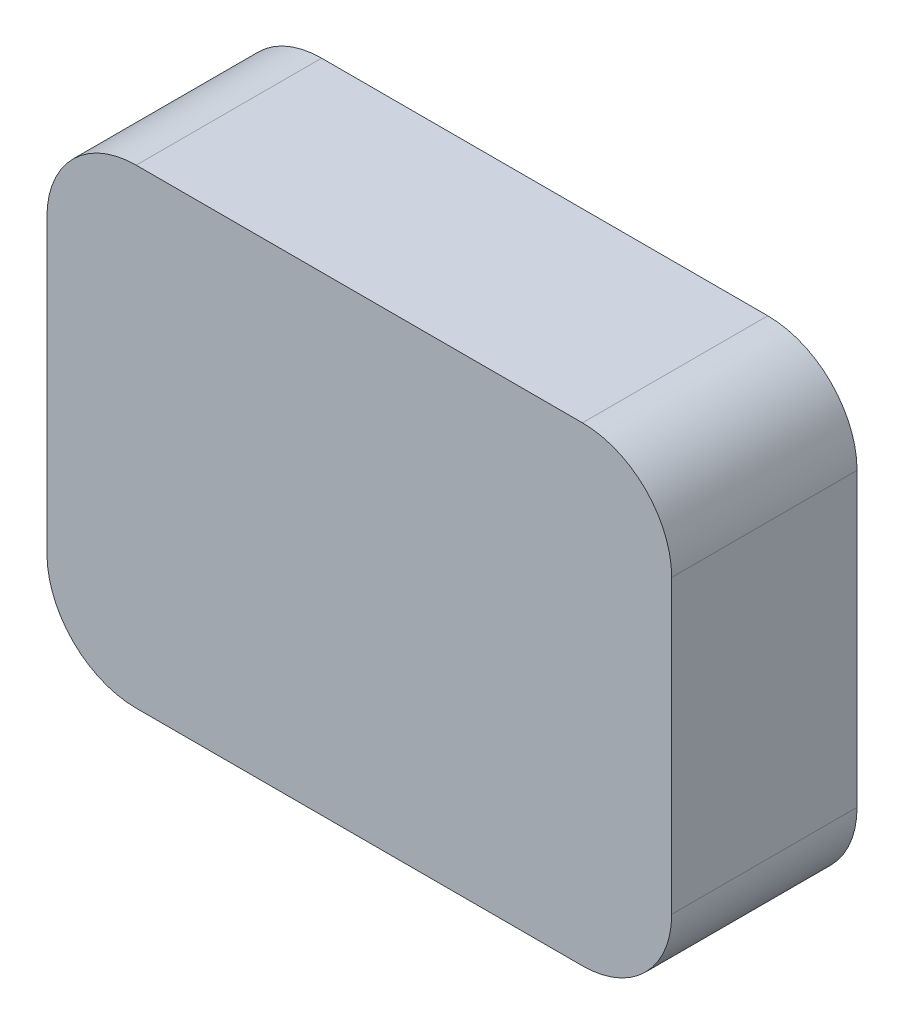
SolidWorks part; units mm, degrees
ref_plane "Plan de face" through (0, 0, 0) normal (0, 0, 1) x (1, 0, 0)
ref_plane "Plan de dessus" through (0, 0, 0) normal (0, 1, 0) x (1, 0, 0)
ref_plane "Plan de droite" through (0, 0, 0) normal (1, 0, 0) x (0, 0, -1)
sketch "Esquisse1" plane through (0, 0, 0) normal (0, 0, 1) x (1, 0, 0)
  line L1 (-26, 27) -> (26, 27)
  line L2 (-36, 17) -> (-36, -17)
  line L3 (-26, -27) -> (26, -27)
  line L4 (36, 17) -> (36, -17)
  line L5 (-36, 27) -> (36, -27) construction
  line L6 (-36, -27) -> (36, 27) construction
  arc A0 (-36, -17) -> (-26, -27) centre (-26, -17) ccw
  arc A1 (26, -27) -> (36, -17) centre (26, -17) ccw
  arc A2 (26, 27) -> (36, 17) centre (26, 17) cw
  arc A3 (-26, 27) -> (-36, 17) centre (-26, 17) ccw
  point P0 (0, 0)
  dimension "D1" = 10
  dimension "D2" = 52
  dimension "D3" = 34
sketch "profil" plane through (0, 0, 0) normal (1, 0, 0) x (0, 0, -1)
  line L0 (0, -25.5219) -> (4.1106, -25.5219)
  line L1 (4.1106, -25.5219) -> (10, -21)
  line L3 (10, -27) -> (0, -27)
  line L4 (0, -27) -> (0, -25.5219)
  line L6 (0, -17) -> (0, -27) construction
  line L7 (0, -27) -> (0, 27) construction
  line L10 (10, -21) -> (10, -27) construction
  line L11 (10, -24) -> (12.7162, -24) construction
  line L12 (10, -25.7405) -> (10, -27) construction
  line L15 (10, -27) -> (10, -26.6)
  line L16 (10, -26.6) -> (9.8, -26.6)
  line L17 (9.8, -26.6) -> (9.8, -25.8)
  line L18 (9.8, -25.8) -> (10, -25.8)
  line L20 (10, -25.8) -> (10, -25.4)
  line L21 (10, -21) -> (10, -21.4)
  line L22 (10, -21.4) -> (9.8, -21.4)
  line L23 (9.8, -21.4) -> (9.8, -22.2)
  line L24 (9.8, -22.2) -> (10, -22.2)
  line L25 (10, -22.2) -> (10, -22.6)
  line L39 (10, -22.6) -> (10.4, -22.6)
  line L54 (10.4, -22.6) -> (10.4, -23)
  line L55 (10.4, -23) -> (10.8, -23)
  line L56 (10.8, -23) -> (10.8, -23.4)
  line L57 (10.8, -23.4) -> (11.2, -23.4)
  line L58 (11.2, -23.4) -> (11.2, -23.8)
  line L59 (11.2, -23.8) -> (11.6, -23.8)
  line L60 (11.6, -23.8) -> (11.6, -24.2)
  line L61 (11.6, -24.2) -> (11.2, -24.2)
  line L62 (11.2, -24.2) -> (11.2, -24.6)
  line L63 (11.2, -24.6) -> (10.8, -24.6)
  line L64 (10.8, -24.6) -> (10.8, -25)
  line L65 (10.8, -25) -> (10.4, -25)
  line L66 (10.4, -25) -> (10.4, -25.4)
  line L67 (10.4, -25.4) -> (10, -25.4)
  dimension "D3" = 10
  dimension "D4" = 6
  dimension "D5" = 0.8
  dimension "D7" = 0.4
  dimension "D1" = 0.4
  dimension "D8" = 0.4
sweep "Balayage1" add profiles "profil" path "Esquisse1"
extrude "Boss.-Extru.1" add sketch "Esquisse1<3>" along normal blind 1.6
sketch "Esquisse1<3>" plane through (0, 0, 0) normal (0, 0, 1) x (1, 0, 0) same geometry as "Esquisse1"
fillet "Congé1" radius 2 9 edges at (-32.0259, 23.0259, 0) (-34.5219, 0, 0) (-32.0259, -23.0259, 0) (-13, -25.5219, 0) (13, -25.5219, 0) (32.0259, -23.0259, 0) (34.5219, 0, 0) (32.0259, 23.0259, 0) (0, 25.5219, 0)
sketch "Esquisse2" plane through (0, 0, 0) normal (0, 0, 1) x (1, 0, 0)
  line L8 (36.4, -17) -> (36.4, 17)
  line L9 (-26, -27.4) -> (26, -27.4)
  line L10 (-36.4, 17) -> (-36.4, -17)
  line L11 (26, 27.4) -> (-26, 27.4)
  line L12 (36.4, -17) -> (36.4, 17)
  line L13 (-26, -27.4) -> (26, -27.4)
  line L14 (-36.4, 17) -> (-36.4, -17)
  line L15 (26, 27.4) -> (-26, 27.4)
  arc A8 (36.4, 17) -> (26, 27.4) centre (26, 17) ccw
  arc A9 (26, -27.4) -> (36.4, -17) centre (26, -17) ccw
  arc A10 (-36.4, -17) -> (-26, -27.4) centre (-26, -17) ccw
  arc A11 (-26, 27.4) -> (-36.4, 17) centre (-26, 17) ccw
  arc A12 (36.4, 17) -> (26, 27.4) centre (26, 17) ccw
  arc A13 (26, -27.4) -> (36.4, -17) centre (26, -17) ccw
  arc A14 (-36.4, -17) -> (-26, -27.4) centre (-26, -17) ccw
  arc A15 (-26, 27.4) -> (-36.4, 17) centre (-26, 17) ccw
  dimension "D1" = 0.4
extrude "Extru.-Mince1" add sketch "Esquisse2" against normal blind 20 and the other way up to surface (1.6 mm away) thin other way up to face at (0, 0, 1.6) thin type one direction reverse wall 0.4
equation "\"buse\"=0.4"
equation "\"coque\"= \"buse\" * 4"
equation "\"diam_silicone\"=3"
equation "\"couche\"=0.2"
equation "\"D1@Boss.-Extru.1\"=\"fond\""
equation "\"fond\"= \"couche\" * 8"
equation "\"D2@Esquisse1\"=\"dim_ext_L@boitier_balaye-1.Part\""
equation "\"D4@profil\"=\"epaisseur_jonction@boitier_balaye-1.Part\""
equation "\"D3@Esquisse1\"=\"dim_ext@boitier_balaye-1.Part\""
equation "\"D8@profil\"=\"couche\"*2"
